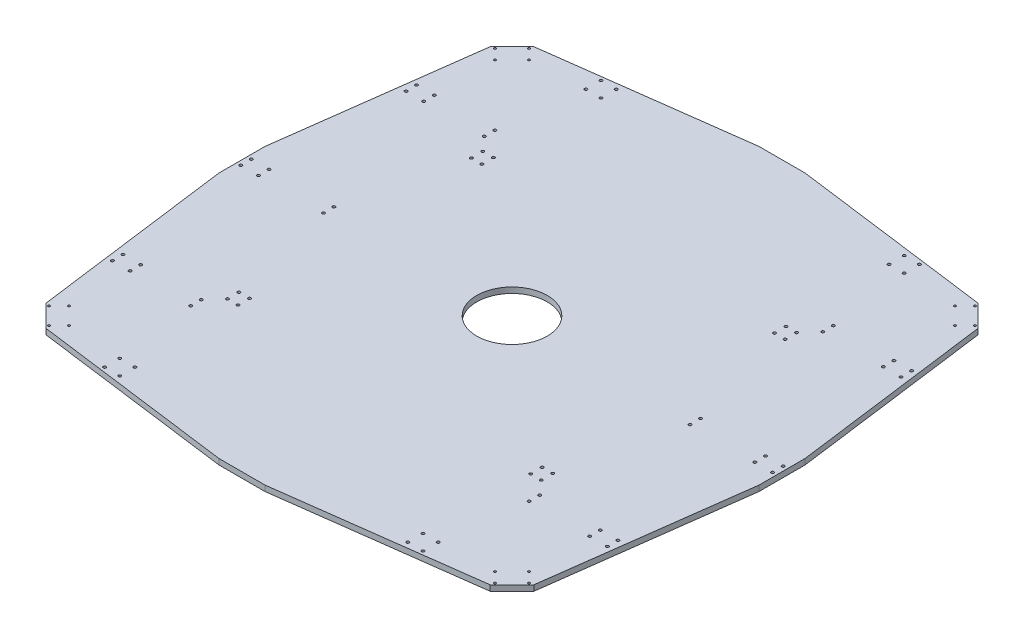
SolidWorks part; units mm, degrees
ref_plane "前视基准面" through (0, 0, 0) normal (0, 0, 1) x (1, 0, 0)
ref_plane "上视基准面" through (0, 0, 0) normal (0, 1, 0) x (1, 0, 0)
ref_plane "右视基准面" through (0, 0, 0) normal (1, 0, 0) x (0, 0, -1)
other "Configuration Table"
sketch "草图1" plane through (0, 0, 0) normal (0, 1, 0) x (1, 0, 0)
  line L0 (-314.9222, 345.9222) -> (-345.9222, 314.9222)
  line L5 (325, -325) -> (-325, 325) construction
  line L6 (325, 325) -> (-325, -325) construction
  line L7 (0, 383.0748) -> (0, -383.0748) construction
  line L8 (383.0748, 0) -> (-383.0748, 0)
  line L9 (314.9222, 345.9222) -> (32.7201, 383.0748)
  line L10 (314.9222, 345.9222) -> (345.9222, 314.9222)
  line L12 (-314.9222, 345.9222) -> (-32.7201, 383.0748)
  line L13 (0, 383.0748) -> (0, 399.6983)
  line L14 (-32.7201, 383.0748) -> (32.7201, 383.0748)
  line L15 (314.9222, -345.9222) -> (32.7201, -383.0748)
  line L16 (-32.7201, -383.0748) -> (32.7201, -383.0748)
  line L17 (-314.9222, -345.9222) -> (-32.7201, -383.0748)
  line L18 (-314.9222, -345.9222) -> (-345.9222, -314.9222)
  line L19 (-345.9222, 314.9222) -> (-383.0748, 32.7201)
  line L20 (-383.0748, -32.7201) -> (-383.0748, 32.7201)
  line L21 (-345.9222, -314.9222) -> (-383.0748, -32.7201)
  line L22 (-345.9222, -314.9222) -> (-314.9222, -345.9222)
  line L23 (345.9222, -314.9222) -> (314.9222, -345.9222)
  line L24 (345.9222, -314.9222) -> (383.0748, -32.7201)
  line L25 (383.0748, 32.7201) -> (383.0748, -32.7201)
  line L26 (345.9222, 314.9222) -> (383.0748, 32.7201)
  line L27 (-337.8712, -313.8296) -> (-342.443, -318.4014)
  line L28 (-314.9222, -345.9222) -> (-293.6978, -324.6978)
  line L29 (-326.1795, -302.1379) -> (-298.6587, -329.6587)
  line L30 (-345.9222, -314.9222) -> (-325, -294)
  line L31 (-326.1795, -302.1379) -> (-329.6587, -298.6587)
  line L32 (-313.4871, -289.4455) -> (-337.8712, -313.8296)
  line L33 (-289.4455, -313.4871) -> (-313.8296, -337.8712)
  line L34 (-313.8296, -337.8712) -> (-318.4014, -342.443)
  circle A1 centre (-326.1795, -302.1379) radius 1.5
  circle A2 centre (-302.1379, -326.1795) radius 1.5
  circle A3 centre (-340.3217, -316.28) radius 1.5
  circle A4 centre (-316.28, -340.3217) radius 1.5
  circle A5 centre (0, 0) radius 50
  circle A6 centre (325.9184, 215.682) radius 2
  circle A7 centre (377.0748, 7.5001) radius 2
  circle A8 centre (350.9184, 215.682) radius 2
  circle A9 centre (325.9184, 200.682) radius 2
  circle A10 centre (350.9184, 200.682) radius 2
  circle A11 centre (352.0748, 7.5001) radius 2
  circle A12 centre (352.0748, -7.5951) radius 2
  circle A13 centre (377.0748, -7.5951) radius 2
  circle A14 centre (325.9184, -200.682) radius 2
  circle A15 centre (350.9184, -200.682) radius 2
  circle A16 centre (325.9184, -215.682) radius 2
  circle A17 centre (350.9184, -215.682) radius 2
  circle A18 centre (-350.9184, -200.682) radius 2
  circle A19 centre (-325.9184, -200.682) radius 2
  circle A20 centre (-350.9184, -215.682) radius 2
  circle A21 centre (-325.9184, -215.682) radius 2
  circle A22 centre (-377.0748, 7.5001) radius 2
  circle A23 centre (-352.0748, 7.5001) radius 2
  circle A24 centre (-377.0748, -7.4999) radius 2
  circle A25 centre (-352.0748, -7.4999) radius 2
  circle A26 centre (-350.9184, 215.682) radius 2
  circle A27 centre (-325.9184, 215.682) radius 2
  circle A28 centre (-350.9184, 200.682) radius 2
  circle A29 centre (-325.9184, 200.682) radius 2
  circle A30 centre (-222.5, 181.0301) radius 2
  circle A31 centre (-207.5, 181.0301) radius 2
  circle A32 centre (-222.5, 164.8255) radius 2
  circle A33 centre (-207.5, 164.8255) radius 2
  circle A34 centre (-207.5, -164.8255) radius 2
  circle A35 centre (-222.5, -164.8255) radius 2
  circle A36 centre (-207.5, -181.0301) radius 2
  circle A37 centre (-222.5, -181.0301) radius 2
  circle A38 centre (207.5, 164.8255) radius 2
  circle A39 centre (222.5, 164.8255) radius 2
  circle A40 centre (207.5, 181.0301) radius 2
  circle A41 centre (222.5, 181.0301) radius 2
  circle A42 centre (207.5, -181.0301) radius 2
  circle A43 centre (207.5, -164.8255) radius 2
  circle A44 centre (222.5, -181.0301) radius 2
  circle A45 centre (222.5, -164.8255) radius 2
  circle A46 centre (-240, 215.682) radius 2
  circle A47 centre (-240, 200.682) radius 2
  circle A50 centre (-240, -215.682) radius 2
  circle A51 centre (-240, -200.682) radius 2
  circle A52 centre (240, 215.682) radius 2
  circle A53 centre (240, 200.682) radius 2
  circle A56 centre (240, -200.682) radius 2
  circle A57 centre (240, -215.682) radius 2
  circle A58 centre (260, 7.5) radius 2 construction
  circle A59 centre (260, -7.5) radius 2 construction
  circle A60 centre (260, 7.5) radius 2
  circle A61 centre (260, -7.5) radius 2
  circle A62 centre (-260, 7.5) radius 2 construction
  circle A64 centre (-260, -7.5) radius 2 construction
  circle A65 centre (-260, -7.5) radius 2
  circle A66 centre (-260, 7.5) radius 2
  point P0 (0, 0)
  point P13 (0, 383.0748)
  point P24 (-330.4222, -330.4222)
  point P44 (-326.1795, -302.1379)
  point P45 (-302.1379, -326.1795)
  dimension "D6" = 3
  dimension "D7" = 20
  dimension "D8" = 100
  dimension "D1" = 650
  dimension "D2" = 650
  dimension "D3" = 31
  dimension "D4" = 142.5
  dimension "D5" = 17
extrude "凸台-拉伸2" add sketch "草图1" along normal blind 8 contours L26 L10 L9 L14 L12 L0 L19 L20 L21 L18 L17 L16 L15 L23 L24 L25 | A2 L29 A1 L32 L27 L22 L34 L33 | A1 L31 L30 L22 L27 L32 | A2 L33 L34 L18 L28 L29 | A5 L8 L20 L21 L30 L31 A1 L29 A2 L28 L17 L16 L15 L23 L24 L25 A65 A61 A56 A51 A50 A45 A44 A43 A42 A36 A34 region at (0, 0, -180.62) region at (1.2637, 0, 180.0646) region at (-336.0431, 0, 308.3956) region at (-322.2706, 0, 322.2706) region at (-308.3956, 0, 336.0431)
sketch "草图2" plane through (0, 8, 0) normal (0, 1, 0) x (1, 0, 0)
  line L0 (0, 0) -> (-330.4222, -330.4222) construction
pattern_circular "阵列(圆周)1" count 4 over 360 about axis through (0, 8, 0) along (0, 1, 0) of face at (-326.1795, 8, 303.6379) of face at (-340.3217, 8, 317.78) of face at (-302.1379, 8, 327.6795) of face at (-316.28, 8, 341.8217)
sketch "草图3" plane through (0, 8, 0) normal (0, 1, 0) x (1, 0, 0)
  line L0 (383.0748, 0) -> (-381.6237, 0)
  line L1 (383.0748, 32.7201) -> (383.0748, -32.7201) construction
  circle A0 centre (-225.7527, 352.0186) radius 2
  circle A1 centre (-204.2473, 352.0186) radius 2
  circle A2 centre (-225.7527, 330.5131) radius 2
  circle A3 centre (-204.2473, 330.5131) radius 2
  circle A4 centre (204.2473, 352.0186) radius 2
  circle A5 centre (225.7527, 352.0186) radius 2
  circle A6 centre (204.2473, 330.5131) radius 2
  circle A7 centre (225.7429, 330.3998) radius 2
  circle A8 centre (225.7429, -330.3998) radius 2
  circle A9 centre (204.2473, -330.5131) radius 2
  circle A10 centre (225.7527, -352.0186) radius 2
  circle A11 centre (204.2473, -352.0186) radius 2
  circle A12 centre (-204.2473, -330.5131) radius 2
  circle A13 centre (-225.7527, -330.5131) radius 2
  circle A14 centre (-204.2473, -352.0186) radius 2
  circle A15 centre (-225.7527, -352.0186) radius 2
  dimension "D1" = 4
extrude "切除-拉伸1" cut sketch "草图3" against normal blind 55 and the other way blind 37 contours A13 | A15 | A12 | A14 | A10 | A9 | A11 | A8 | A2 | A0 | A3 | A1 | A7 | A5 | A6 | A4 region at (-225.7527, 8, -352.0186) region at (-204.2473, 8, -352.0186) region at (-225.7527, 8, -330.5131) region at (-204.2473, 8, -330.5131) region at (204.2473, 8, -352.0186) region at (225.7527, 8, -352.0186) region at (204.2473, 8, -330.5131) region at (225.7429, 8, -330.3998) region at (225.7429, 8, 330.3998) region at (204.2473, 8, 330.5131) region at (225.7527, 8, 352.0186) region at (204.2473, 8, 352.0186) region at (-204.2473, 8, 330.5131) region at (-225.7527, 8, 330.5131) region at (-204.2473, 8, 352.0186) region at (-225.7527, 8, 352.0186)
